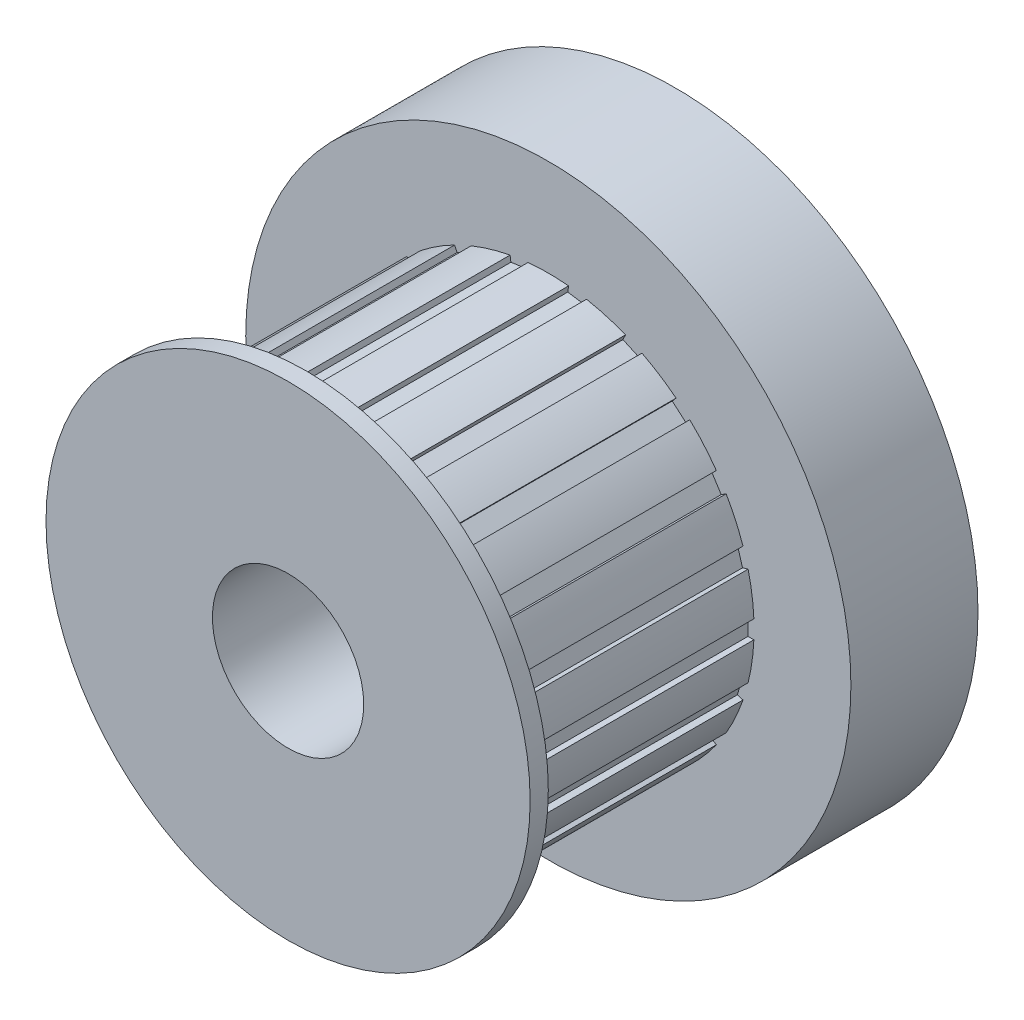
SolidWorks part; units mm, degrees
ref_plane "Front Plane" through (0, 0, 0) normal (0, 0, 1) x (1, 0, 0)
ref_plane "Top Plane" through (0, 0, 0) normal (0, 1, 0) x (1, 0, 0)
ref_plane "Right Plane" through (0, 0, 0) normal (1, 0, 0) x (0, 0, -1)
sketch "Sketch1" plane through (0, 0, 0) normal (0, 0, 1) x (1, 0, 0)
  circle A0 centre (0, 0) radius 10.16
  dimension "D1" = 20.32
extrude "Boss-Extrude1" add sketch "Sketch1" against normal blind 0.762
sketch "Sketch2" plane through (0, 0, -0.762) normal (0, 0, -1) x (-1, 0, 0)
  circle A0 centre (0, 0) radius 8.636
  dimension "D1" = 17.272
extrude "Boss-Extrude2" add sketch "Sketch2" along normal blind 10.16
sketch "Sketch3" plane through (0, 0, -10.922) normal (0, 0, -1) x (-1, 0, 0)
  circle A0 centre (0, 0) radius 12.7
  dimension "D1" = 25.4
extrude "Boss-Extrude3" add sketch "Sketch3" along normal blind 5.334
sketch "Sketch4" plane through (0, 0, 0) normal (0, 0, 1) x (1, 0, 0)
  circle A0 centre (0, 0) radius 3.175
  dimension "D1" = 6.35
extrude "Cut-Extrude1" cut sketch "Sketch4" against normal blind 25.654
ref_plane "Plane2" through (-8.636, 0, 0) normal (-1, 0, 0) x (0, 0, 1)
sketch "Sketch5" plane through (-8.636, 0, 0) normal (-1, 0, 0) x (0, 0, 1)
  line L0 (-10.922, -8.636) -> (-10.922, 8.636) construction
  line L1 (-10.922, 0.381) -> (-0.762, 0.381)
  line L2 (-10.922, 0.381) -> (-10.922, -0.381)
  line L3 (-10.922, -0.381) -> (-0.762, -0.381)
  line L4 (-0.762, 0.381) -> (-0.762, -0.381)
  line L5 (-0.762, 8.636) -> (-0.762, -8.636) construction
  point P8 (-10.922, 0)
  dimension "D1" = 0.762
extrude "Cut-Extrude2" cut sketch "Sketch5" against normal blind 0.254
ref_axis "Axis1" through (0, 0, -16.256) along (0, 0, 1)
pattern_circular "CirPattern1" count 22 over 360 about axis through (0, 0, -16.256) along (0, 0, 1) of "Cut-Extrude2"
